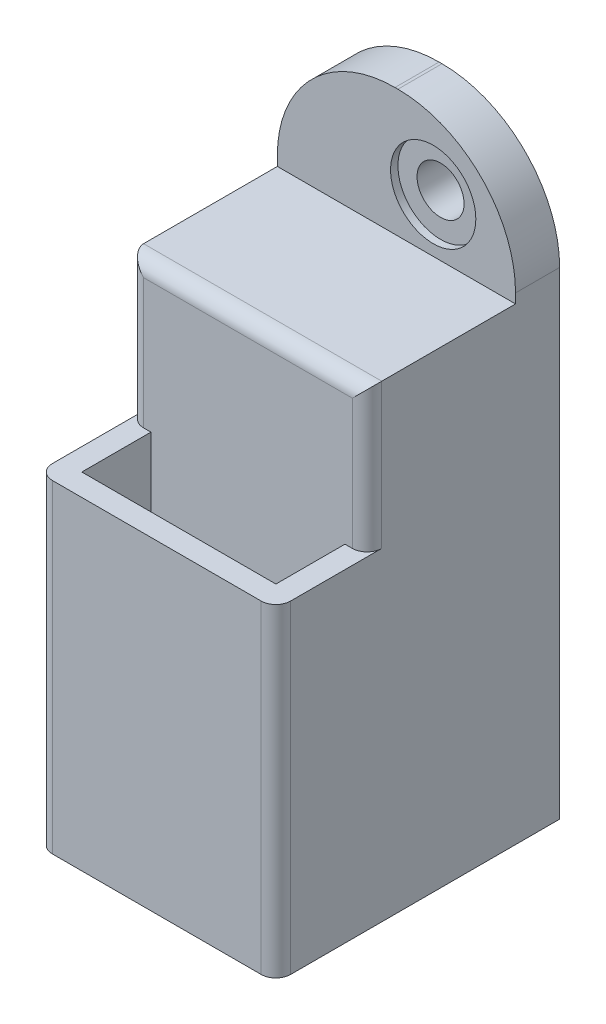
SolidWorks part; units mm, degrees
ref_plane "Alzado" through (0, 0, 0) normal (0, 0, 1) x (1, 0, 0)
ref_plane "Planta" through (0, 0, 0) normal (0, 1, 0) x (1, 0, 0)
ref_plane "Vista lateral" through (0, 0, 0) normal (1, 0, 0) x (0, 0, -1)
sketch "Croquis2" plane through (0, 0, 0) normal (0, 1, 0) x (1, 0, 0)
  line L0 (-1.5, 1.5) -> (14.7, 1.5)
  line L1 (0, 0) -> (13.2, 0)
  line L2 (0, 0) -> (0, -6.2)
  line L3 (0, -6.2) -> (13.2, -6.2)
  line L4 (13.2, 0) -> (13.2, -6.2)
  line L5 (14.7, 1.5) -> (14.7, -7.7)
  line L6 (-1.5, -7.7) -> (14.7, -7.7)
  line L7 (-1.5, 1.5) -> (-1.5, -7.7)
  dimension "D1" = 13.2
  dimension "D2" = 6.2
  dimension "D3" = 1.5
extrude "Saliente-Extruir1" add sketch "Croquis2" along normal blind 6.5
sketch "Croquis3" plane through (0, 0, -1.5) normal (0, 0, -1) x (-1, 0, 0)
  line L1 (1.5, 0) -> (-14.7, 0)
  line L2 (1.5, 0) -> (1.5, 12)
  line L3 (1.5, 12) -> (-14.7, 12)
  line L4 (-14.7, 0) -> (-14.7, 12)
  line L6 (-14.7, 0) -> (1.5, 0) construction
  line L8 (-14.7, 6.5) -> (-14.7, 0) construction
  line L9 (1.5, 6.5) -> (1.5, 0) construction
  dimension "D1" = 12
extrude "Saliente-Extruir2" add sketch "Croquis3" along normal blind 2
sketch "Croquis4" plane through (0, 0, -3.5) normal (0, 0, -1) x (-1, 0, 0)
  line L10 (1.5, 0) -> (1.5, 12) construction
  line L11 (1.5, 12) -> (-14.7, 12) construction
  line L12 (-14.7, 12) -> (-14.7, 0) construction
  line L13 (1.5, 0) -> (1.5, 12)
  line L14 (1.5, 12) -> (-14.7, 12)
  line L15 (-14.7, 12) -> (-14.7, 0)
  line L16 (-0.3, 0) -> (-0.3, 11)
  line L17 (-14.7, 0) -> (1.5, 0) construction
  line L18 (-0.3, 11) -> (-12.9, 11)
  line L19 (-12.9, 11) -> (-12.9, 0)
  line L20 (1.5, 0) -> (-0.3, 0)
  line L21 (-12.9, 0) -> (-14.7, 0)
  dimension "D1" = 1
  dimension "D2" = 1.8
  dimension "D3" = 1.8
extrude "Saliente-Extruir3" add sketch "Croquis4" along normal blind 8.1
sketch "Croquis5" plane through (0, 12, 0) normal (0, 1, 0) x (1, 0, 0)
  line L0 (-1.5, 11.6) -> (-1.5, 1.5) construction
  line L1 (14.7, 11.6) -> (-1.5, 11.6)
  line L2 (14.7, 11.6) -> (14.7, 8.6)
  line L3 (14.7, 8.6) -> (-1.5, 8.6)
  line L4 (-1.5, 11.6) -> (-1.5, 8.6)
  dimension "D1" = 3
extrude "Saliente-Extruir4" add sketch "Croquis5" along normal blind 13
sketch "Croquis6" plane through (0, 0, -8.6) normal (0, 0, 1) x (1, 0, 0)
  line L0 (14.7, 25) -> (14.7, 12) construction
  line L1 (-1.5, 25) -> (14.7, 25) construction
  circle A0 centre (9.1, 20) radius 1.6
  dimension "D1" = 3.2
  dimension "D2" = 5.6
  dimension "D3" = 5
extrude "Cortar-Extruir1" cut sketch "Croquis6" against normal up to surface (3 mm away) up to face at (6.6, 9, -11.6)
sketch "Croquis7" plane through (0, 0, -1.5) normal (0, 0, 1) x (1, 0, 0)
  line L0 (-1.5, 6.5) -> (-1.5, 12) construction
  line L1 (14.7, 6.5) -> (-1.5, 6.5)
  line L2 (14.7, 6.5) -> (14.7, 8.5)
  line L3 (14.7, 8.5) -> (-1.5, 8.5)
  line L4 (-1.5, 6.5) -> (-1.5, 8.5)
  dimension "D1" = 2
extrude "Saliente-Extruir5" add sketch "Croquis7" along normal blind 3
sketch "Croquis8" plane through (0, 0, -8.6) normal (0, 0, 1) x (1, 0, 0)
  circle A0 centre (9.1, 20) radius 2.9
  dimension "D1" = 5.8
extrude "Cortar-Extruir2" cut sketch "Croquis8" against normal blind 0.5
fillet "Redondeo1" radius 1 2 edges at (-1.5, 3.25, 7.7) (14.7, 3.25, 7.7)
fillet "Redondeo6" radius 8 2 edges at (14.7, 25, -10.1) (-1.5, 25, -10.1)
sketch "Croquis9" plane through (0, 0, 0) normal (0, -1, 0) x (1, 0, 0)
  line L0 (0, 0) -> (0, 6.2) construction
  line L1 (0, 6.2) -> (13.2, 6.2) construction
  line L2 (13.2, 6.2) -> (13.2, 0) construction
  line L3 (13.2, 0) -> (0, 0) construction
  line L4 (0, 0) -> (0, 6.2)
  line L5 (0, 6.2) -> (13.2, 6.2)
  line L6 (13.2, 6.2) -> (13.2, 0)
  line L7 (13.2, 0) -> (0, 0)
  line L8 (13.7, 7.7) -> (-0.5, 7.7)
  line L9 (-1.5, 6.7) -> (-1.5, -11.6)
  line L10 (-1.5, -11.6) -> (0.3, -11.6)
  line L11 (0.3, -11.6) -> (0.3, -3.5)
  line L12 (0.3, -3.5) -> (12.9, -3.5)
  line L13 (12.9, -3.5) -> (12.9, -11.6)
  line L14 (12.9, -11.6) -> (14.7, -11.6)
  line L15 (14.7, -11.6) -> (14.7, 6.7)
  line L16 (13.7, 7.7) -> (-0.5, 7.7)
  line L17 (-1.5, 6.7) -> (-1.5, -11.6)
  line L18 (-1.5, -11.6) -> (0.3, -11.6)
  line L19 (0.3, -11.6) -> (0.3, -3.5)
  line L20 (0.3, -3.5) -> (12.9, -3.5)
  line L21 (12.9, -3.5) -> (12.9, -11.6)
  line L22 (12.9, -11.6) -> (14.7, -11.6)
  line L23 (14.7, -11.6) -> (14.7, 6.7)
  arc A2 (-0.5, 7.7) -> (-1.5, 6.7) centre (-0.5, 6.7) ccw
  arc A3 (14.7, 6.7) -> (13.7, 7.7) centre (13.7, 6.7) ccw
  arc A4 (-0.5, 7.7) -> (-1.5, 6.7) centre (-0.5, 6.7) ccw
  arc A5 (14.7, 6.7) -> (13.7, 7.7) centre (13.7, 6.7) ccw
  dimension "D1" = 0
extrude "Saliente-Extruir6" add sketch "Croquis9" along normal blind 3.5
sketch "Croquis10" plane through (0, 6.5, 0) normal (0, -1, 0) x (1, 0, 0)
  line L4 (0, 1.5) -> (0, 0)
  line L5 (0, 0) -> (13.2, 0)
  line L6 (13.2, 0) -> (13.2, 1.5)
  line L7 (13.2, 1.5) -> (0, 1.5)
  line L8 (0, 1.5) -> (0, 0)
  line L9 (0, 0) -> (13.2, 0)
  line L10 (13.2, 0) -> (13.2, 1.5)
  line L11 (13.2, 1.5) -> (0, 1.5)
  dimension "D1" = 0
extrude "Saliente-Extruir7" add sketch "Croquis10" along normal blind 3.5
sketch "Croquis11" plane through (0, -3.5, 0) normal (0, -1, 0) x (1, 0, 0)
  line L0 (0, 6.2) -> (0, 0) construction
  line L1 (13.2, 6.2) -> (0, 6.2) construction
  line L2 (13.2, 0) -> (13.2, 6.2) construction
  line L3 (0, 0) -> (13.2, 0) construction
  line L4 (0, 6.2) -> (0, 0)
  line L5 (13.2, 6.2) -> (0, 6.2)
  line L6 (13.2, 0) -> (13.2, 6.2)
  line L7 (0, 0) -> (13.2, 0)
  line L8 (13.7, 7.7) -> (-0.5, 7.7)
  line L9 (-1.5, 6.7) -> (-1.5, -11.6)
  line L10 (-1.5, -11.6) -> (0.3, -11.6)
  line L11 (0.3, -11.6) -> (0.3, -3.5)
  line L12 (0.3, -3.5) -> (12.9, -3.5)
  line L13 (12.9, -3.5) -> (12.9, -11.6)
  line L14 (12.9, -11.6) -> (14.7, -11.6)
  line L15 (14.7, -11.6) -> (14.7, 6.7)
  line L16 (13.7, 7.7) -> (-0.5, 7.7)
  line L17 (-1.5, 6.7) -> (-1.5, -11.6)
  line L18 (-1.5, -11.6) -> (0.3, -11.6)
  line L19 (0.3, -11.6) -> (0.3, -3.5)
  line L20 (0.3, -3.5) -> (12.9, -3.5)
  line L21 (12.9, -3.5) -> (12.9, -11.6)
  line L22 (12.9, -11.6) -> (14.7, -11.6)
  line L23 (14.7, -11.6) -> (14.7, 6.7)
  arc A2 (14.7, 6.7) -> (13.7, 7.7) centre (13.7, 6.7) ccw
  arc A3 (-0.5, 7.7) -> (-1.5, 6.7) centre (-0.5, 6.7) ccw
  arc A4 (14.7, 6.7) -> (13.7, 7.7) centre (13.7, 6.7) ccw
  arc A5 (-0.5, 7.7) -> (-1.5, 6.7) centre (-0.5, 6.7) ccw
  dimension "D1" = 0
extrude "Saliente-Extruir8" add sketch "Croquis11" along normal blind 12
sketch "Croquis12" plane through (0, 3, 0) normal (0, -1, 0) x (1, 0, 0)
  line L4 (13.2, 1.5) -> (0, 1.5)
  line L5 (0, 1.5) -> (0, 0)
  line L6 (0, 0) -> (13.2, 0)
  line L7 (13.2, 0) -> (13.2, 1.5)
  line L8 (13.2, 1.5) -> (0, 1.5)
  line L9 (0, 1.5) -> (0, 0)
  line L10 (0, 0) -> (13.2, 0)
  line L11 (13.2, 0) -> (13.2, 1.5)
  dimension "D1" = 0
extrude "Saliente-Extruir9" add sketch "Croquis12" along normal blind 12
sketch "Croquis13" plane through (0, 0, -8.6) normal (0, 0, 1) x (1, 0, 0)
  line L0 (14.7, 17) -> (14.7, 12) construction
  line L1 (14.7, 16.35) -> (-1.5, 16.35)
  line L2 (14.7, 16.35) -> (14.7, 8.5)
  line L3 (14.7, 8.5) -> (-1.5, 8.5)
  line L4 (-1.5, 16.35) -> (-1.5, 8.5)
  line L5 (-1.5, 17) -> (-1.5, 12) construction
  line L6 (14.7, 8.5) -> (-1.5, 8.5) construction
  line L7 (14.7, 8.5) -> (-1.5, 8.5) construction
  line L8 (-1.5, 12) -> (14.7, 12) construction
  point P8 (-1.5, 6.9899)
  point P9 (-1.5, 8.5)
  dimension "D1" = 4.35
extrude "Saliente-Extruir10" add sketch "Croquis13" along normal up to surface (10.1 mm away) up to face at (6.6, 3.125, 1.5)
sketch "Croquis14" plane through (0, 0, -11.6) normal (0, 0, -1) x (-1, 0, 0)
  line L0 (-0.3, 11) -> (-0.3, 8.5) construction
  line L1 (-12.9, 8.5) -> (-0.3, 8.5)
  line L2 (-12.9, 8.5) -> (-12.9, 15)
  line L3 (-12.9, 15) -> (-0.3, 15)
  line L4 (-0.3, 8.5) -> (-0.3, 15)
  point P7 (-12.9, 16.2331)
  dimension "D1" = 6.5
extrude "Cortar-Extruir3" cut sketch "Croquis14" against normal up to surface (8.1 mm away) up to face at (6.6, -3.5, -3.5)
fillet "Redondeo7" radius 1 3 edges at (6.6, 16.35, 1.5) (-1.5, 11.425, 1.5) (14.7, 11.425, 1.5)
